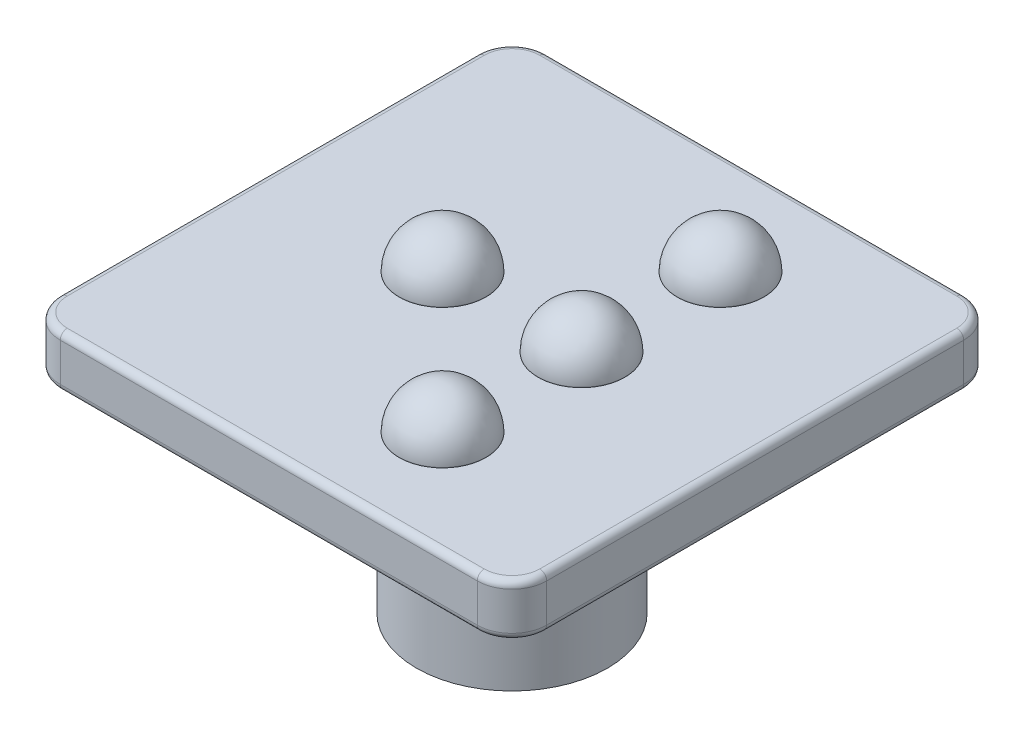
SolidWorks part; units mm, degrees
ref_plane "Front Plane" through (0, 0, 0) normal (0, 0, 1) x (1, 0, 0)
ref_plane "Top Plane" through (0, 0, 0) normal (0, 1, 0) x (1, 0, 0)
ref_plane "Right Plane" through (0, 0, 0) normal (1, 0, 0) x (0, 0, -1)
sketch "Sketch1" plane through (0, 0, 0) normal (0, 1, 0) x (1, 0, 0)
  line L1 (-7.3247, 4.3967) -> (4.6753, 4.3967)
  line L2 (-8.3247, 3.3967) -> (-8.3247, -8.6033)
  line L3 (-7.3247, -9.6033) -> (4.6753, -9.6033)
  line L4 (5.6753, 3.3967) -> (5.6753, -8.6033)
  arc A0 (-8.3247, -8.6033) -> (-7.3247, -9.6033) centre (-7.3247, -8.6033) ccw
  arc A1 (4.6753, -9.6033) -> (5.6753, -8.6033) centre (4.6753, -8.6033) ccw
  arc A2 (4.6753, 4.3967) -> (5.6753, 3.3967) centre (4.6753, 3.3967) cw
  arc A3 (-7.3247, 4.3967) -> (-8.3247, 3.3967) centre (-7.3247, 3.3967) ccw
  point P8 (5.6753, -9.6033)
  point P11 (5.6753, 4.3967)
  point P14 (-8.3247, 4.3967)
  dimension "D3" = 1
  dimension "D1" = 14
  dimension "D2" = 14
extrude "Boss-Extrude1" add sketch "Sketch1" along normal blind 1.5
sketch "Sketch2" plane through (0, 0, 0) normal (0, -1, 0) x (1, 0, 0)
  line L0 (-7.3247, 9.6033) -> (4.6753, 9.6033) construction
  line L1 (5.6753, 8.6033) -> (5.6753, -3.3967) construction
  line L2 (-1.3247, -4.3967) -> (-1.3247, 9.6033) construction
  line L3 (-8.3247, 2.6033) -> (5.6753, 2.6033) construction
  line L4 (-8.3247, -3.3967) -> (-8.3247, 8.6033) construction
  circle A0 centre (-1.3247, 2.6033) radius 2.75
  dimension "D1" = 7
  dimension "D2" = 7
extrude "Boss-Extrude2" add sketch "Sketch2" along normal blind 6
sketch "Sketch3" plane through (0, -6, 0) normal (0, -1, 0) x (1, 0, 0)
  line L0 (-1.3247, 5.3533) -> (-1.3247, -0.1467) construction
  line L1 (-3.3247, 3.1533) -> (0.6753, 3.1533)
  line L2 (-3.3247, 3.1533) -> (-3.3247, 2.0533)
  line L3 (-3.3247, 2.0533) -> (0.6753, 2.0533)
  line L4 (0.6753, 3.1533) -> (0.6753, 2.0533)
  line L5 (-1.8747, 4.6033) -> (-0.7747, 4.6033)
  line L6 (-1.8747, 4.6033) -> (-1.8747, 0.6033)
  line L7 (-1.8747, 0.6033) -> (-0.7747, 0.6033)
  line L8 (-0.7747, 4.6033) -> (-0.7747, 0.6033)
  line L9 (-4.0747, 2.6033) -> (1.4253, 2.6033) construction
  circle A3 centre (-1.3247, 2.6033) radius 2.75 construction
  circle A4 centre (-1.3247, 2.6033) radius 2.75 construction
  dimension "D7" = 0.55
  dimension "D1" = 4
  dimension "D2" = 1.1
  dimension "D3" = 1.1
  dimension "D4" = 4
  dimension "D8" = 0.55
extrude "Cut-Extrude1" cut sketch "Sketch3" against normal blind 6 contours L8 L5 L6 L1 | L1 L8 L3 L4 | L8 L1 L6 L3 | L6 L1 L2 L3 | L8 L3 L6 L7 region at (-2.5997, -6, 2.6033) region at (-1.3247, -6, 3.8783) region at (-1.3247, -6, 2.6033) region at (-0.0497, -6, 2.6033) region at (-1.3247, -6, 1.3283)
chamfer "Chamfer1" distance 0.3 angle 45 12 edges at (-1.3247, -6, 0.6033) (-1.8747, -6, 1.3283) (-2.5997, -6, 2.0533) (-3.3247, -6, 2.6033) (-2.5997, -6, 3.1533) (-0.7747, -6, 1.3283) (-0.0497, -6, 2.0533) (0.6753, -6, 2.6033) (-0.0497, -6, 3.1533) (-0.7747, -6, 3.8783) (-1.3247, -6, 4.6033) (-1.8747, -6, 3.8783)
fillet "Fillet1" radius 1 1 edges at (-1.3247, 0, -0.1467)
sketch "Sketch4" plane through (0, 1.5, 0) normal (0, 1, 0) x (1, 0, 0)
  line L0 (-1.3247, 4.3967) -> (-1.3247, -9.6033) construction
  line L1 (4.6753, 4.3967) -> (-7.3247, 4.3967) construction
  line L2 (-7.3247, -9.6033) -> (4.6753, -9.6033) construction
  line L3 (5.6753, -2.6033) -> (-8.3247, -2.6033) construction
  line L4 (-8.3247, 3.3967) -> (-8.3247, -8.6033) construction
  line L5 (5.6753, -8.6033) -> (5.6753, 3.3967) construction
  line L6 (-3.3247, 4.3967) -> (-3.3247, -9.6033) construction
  line L7 (0.6753, 4.3967) -> (0.6753, -9.6033) construction
  line L8 (-8.3247, 1.3967) -> (5.6753, 1.3967) construction
  line L9 (5.6753, -6.6033) -> (-8.3247, -6.6033) construction
  circle A1 centre (0.6753, -2.6033) radius 1.25
  circle A2 centre (-3.3247, -2.6033) radius 1.25
  circle A4 centre (0.6753, -6.6033) radius 1.25
  circle A5 centre (0.6753, 1.3967) radius 1.25
  dimension "D1" = 4
  dimension "D2" = 4
  dimension "D3" = 2
  dimension "D4" = 2
extrude "Boss-Extrude3" add sketch "Sketch4" along normal blind 0.01
dome "Dome2" faces to dome 1 distance 1.25 reverse direction no elliptical dome no face at (0.6753, 1.51, -0.1467) parameters "D1"=1.25
dome "Dome3" faces to dome 1 distance 1.25 reverse direction no elliptical dome no face at (-3.3247, 1.51, 3.8533) parameters "D1"=1.25
dome "Dome4" faces to dome 1 distance 1.25 reverse direction no elliptical dome no face at (0.6753, 1.51, 3.8533) parameters "D1"=1.25
dome "Dome6" faces to dome 1 distance 1.25 reverse direction no elliptical dome no face at (0.6753, 1.51, 7.8533) parameters "D1"=1.25
fillet "Fillet3" radius 0.2 16 edges at (5.3824, 1.5, -4.1038) (5.6753, 1.5, 2.6033) (5.3824, 1.5, 9.3104) (-1.3247, 1.5, 9.6033) (-8.0318, 1.5, 9.3104) (-8.0318, 1.5, -4.1038) (-8.3247, 1.5, 2.6033) (-1.3247, 1.5, -4.3967) (5.3824, 0, 9.3104) (5.6753, 0, 2.6033) (5.3824, 0, -4.1038) (-1.3247, 0, -4.3967) (-8.0318, 0, -4.1038) (-8.3247, 0, 2.6033) (-8.0318, 0, 9.3104) (-1.3247, 0, 9.6033)
